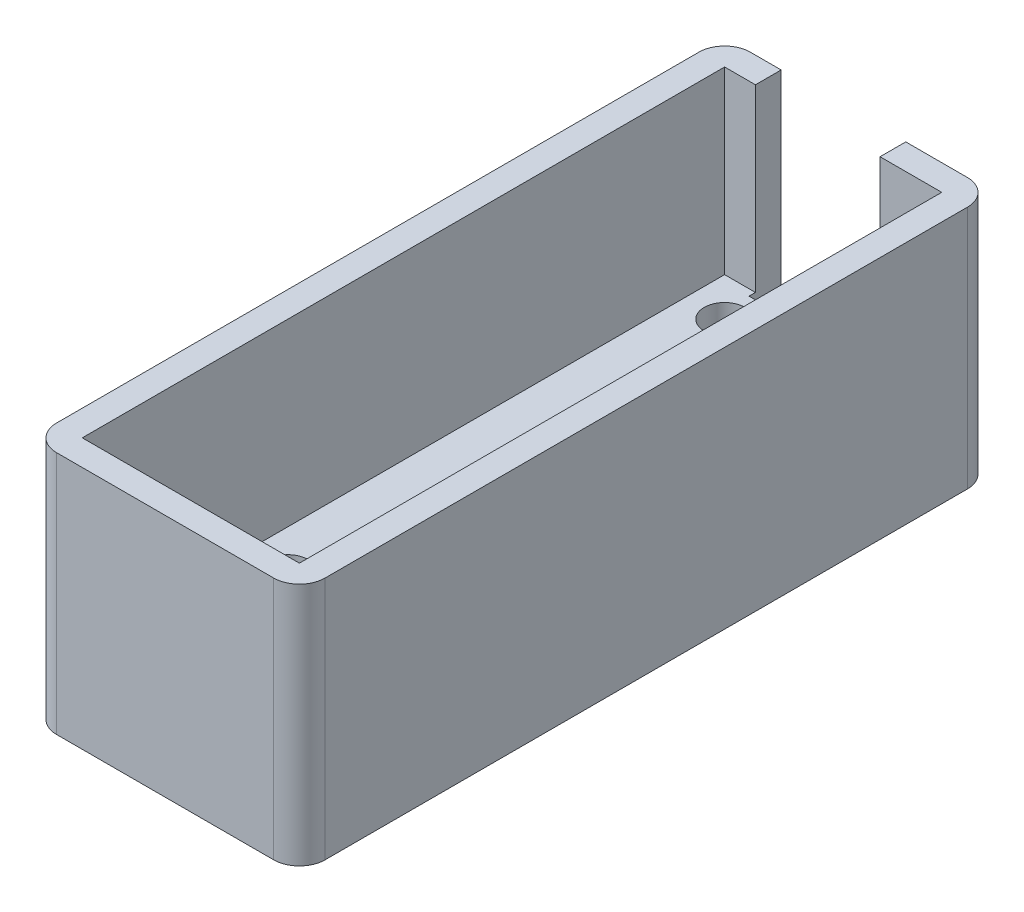
SolidWorks part; units mm, degrees
ref_plane "Front" through (0, 0, 0) normal (0, 0, 1) x (1, 0, 0)
ref_plane "Top" through (0, 0, 0) normal (0, 1, 0) x (1, 0, 0)
ref_plane "Right" through (0, 0, 0) normal (1, 0, 0) x (0, 0, -1)
sketch "Sketch1" plane through (0, 0, 0) normal (0, 1, 0) x (1, 0, 0)
  line L0 (0, 0) -> (21.463, 0)
  line L1 (0, 0) -> (0, 63.5)
  line L2 (0, 63.5) -> (21.463, 63.5)
  line L3 (21.463, 63.5) -> (21.463, 0)
  line L4 (-2.54, -2.54) -> (24.003, -2.54)
  line L5 (24.003, 66.04) -> (24.003, -2.54)
  line L6 (-2.54, 66.04) -> (24.003, 66.04)
  line L7 (-2.54, -2.54) -> (-2.54, 66.04)
  dimension "D1" = 21.463
  dimension "D2" = 63.5
  dimension "D3" = 2.54
extrude "Boss-Extrude1" add sketch "Sketch1" along normal blind 17.78 contours L7 L4 L5 L6 L2 L3 L0 L1 region at (-1.8046, 0, -31.75)
extrude "Boss-Extrude2" add sketch "Sketch1<4>" against normal blind 6.35 contours L3 L2 L1 L0 | L7 L4 L5 L6 L2 L3 L0 L1 region at (10.7315, 0, -31.75) region at (-1.8046, 0, -31.75)
sketch "Sketch1<4>" plane through (0, 0, 0) normal (0, 1, 0) x (1, 0, 0) same geometry as "Sketch1"
sketch "Sketch2" plane through (0, 0, -66.04) normal (0, 0, -1) x (-1, 0, 0)
  line L0 (2.54, 17.78) -> (-24.003, 17.78) construction
  line L1 (-15.367, 17.78) -> (-3.048, 17.78)
  line L2 (-15.367, 17.78) -> (-15.367, -0.635)
  line L3 (-15.367, -0.635) -> (-3.048, -0.635)
  line L4 (-3.048, 17.78) -> (-3.048, -0.635)
  line L5 (-24.003, 17.78) -> (-24.003, -6.35) construction
  line L6 (2.54, 17.78) -> (2.54, -6.35) construction
  line L7 (2.54, -6.35) -> (-24.003, -6.35) construction
  dimension "D1" = 8.636
  dimension "D2" = 5.588
  dimension "D3" = 5.715
extrude "Cut-Extrude1" cut sketch "Sketch2" against normal blind 3.175
sketch "Sketch3" plane through (0, 0, 0) normal (0, 1, 0) x (1, 0, 0)
  line L0 (0, 12.7) -> (21.463, 12.7)
  line L3 (0, 0) -> (21.463, 0) construction
  line L4 (0, 12.7) -> (0, 0)
  line L5 (0, 0) -> (21.463, 0)
  line L6 (21.463, 0) -> (21.463, 12.7)
  line L8 (21.463, 63.5) -> (21.463, 0) construction
  dimension "D1" = 12.7
extrude "Boss-Extrude3" add sketch "Sketch3" along normal blind 5.08
sketch "Sketch4" plane through (0, 5.08, 0) normal (0, 1, 0) x (1, 0, 0)
  line L1 (0, 4.4476) -> (21.463, 4.4476) construction
  line L4 (21.463, 0) -> (21.463, 12.7) construction
  line L5 (0, 12.7) -> (0, 0) construction
  circle A1 centre (9.2315, 4.4476) radius 2.1336
  dimension "D1" = 4.2672
extrude "Cut-Extrude2" cut sketch "Sketch4" against normal through all
fillet "Fillet1" radius 2.54 5 edges at (24.003, 5.715, -66.04) (24.003, 5.715, 2.54) (-2.54, 5.715, 2.54) (-2.54, 5.715, -66.04) (10.7315, 5.08, -12.7)
sketch "Sketch7" plane through (0, 0, 0) normal (0, 1, 0) x (1, 0, 0)
  line L0 (0, 63.5) -> (3.048, 63.5) construction
  line L1 (0, 12.7) -> (0, 63.5) construction
  line L2 (3.81, 59.69) -> (0, 59.69) construction
  line L6 (3.81, 59.69) -> (3.81, 63.5) construction
  line L8 (17.653, 63.5) -> (17.653, 59.69) construction
  line L9 (17.653, 59.69) -> (21.463, 59.69) construction
  line L11 (21.463, 63.5) -> (21.463, 12.7) construction
  line L12 (3.81, 16.51) -> (3.81, 12.7) construction
  line L14 (17.653, 16.51) -> (17.653, 12.7) construction
  line L16 (21.463, 12.7) -> (0, 12.7) construction
  point P0 (3.81, 16.51)
  point P2 (17.653, 16.51)
  point P4 (17.653, 59.69)
  point P6 (3.81, 59.69)
  dimension "D2" = 3.81
hole_wizard "#10-32 Tapped Hole1" positions "Sketch7" profile "Sketch6" tap size "#10-32" standard "ANSI Inch"
cosmetic thread "Hole Thread1" parameters "D1"=9.652, "D2"=4.826
cosmetic thread "Hole Thread2" parameters "D1"=9.652, "D2"=4.826
cosmetic thread "Hole Thread3" parameters "D1"=9.652, "D2"=4.826
cosmetic thread "Hole Thread4" parameters "D1"=9.652, "D2"=4.826
sketch "Sketch6" plane through (3.81, 0, -16.51) normal (1, 0, 0) x (0, 0, 1)
  line L0 (0, 0) -> (0, 13.2529)
  line L1 (0, 13.2529) -> (2.0193, 12.0396)
  line L2 (2.0193, 12.0396) -> (2.0193, 0)
  line L5 (2.0193, 0) -> (0, 0)
  line L10 (0, 13.2529) -> (-2.0193, 12.0396) construction
  line L11 (0, -6.35) -> (0, 107.95) construction
  dimension "Tap Drill Dia." = 4.0386
  dimension "Tap Drill Depth" = 12.0396
  dimension "Drill Angle" = 118
